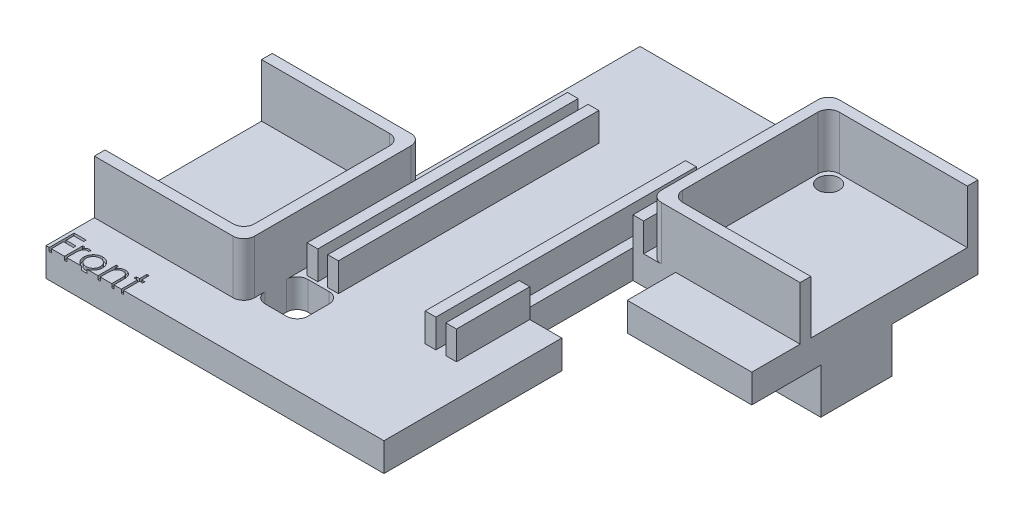
SolidWorks part; units mm, degrees
ref_plane "Front Plane" through (0, 0, 0) normal (0, 0, 1) x (1, 0, 0)
ref_plane "Top Plane" through (0, 0, 0) normal (0, 1, 0) x (1, 0, 0)
ref_plane "Right Plane" through (0, 0, 0) normal (1, 0, 0) x (0, 0, -1)
sketch "Sketch1" plane through (0, 0, 0) normal (0, 1, 0) x (1, 0, 0)
  line L1 (-15, 33) -> (32.5, 33)
  line L2 (-32.5, -1.2) -> (-32.5, -33)
  line L3 (-32.5, -33) -> (15, -33)
  line L4 (32.5, 33) -> (32.5, 1.2)
  line L5 (-15, 15.2308) -> (15, -15.2308) construction
  line L6 (-32.5, -33) -> (32.5, 33) construction
  line L9 (32.5, 1.2) -> (15, 1.2)
  line L10 (15, -33) -> (15, 1.2)
  line L13 (-32.5, -1.2) -> (-15, -1.2)
  line L14 (-15, 33) -> (-15, -1.2)
  point P0 (0, 0)
  dimension "D3" = 17.5
  dimension "D4" = 17.5
  dimension "D5" = 34.2
  dimension "D6" = 34.2
extrude "Boss-Extrude1" add sketch "Sketch1" along normal blind 4
sketch "Sketch2" plane through (0, 4, 0) normal (0, 1, 0) x (1, 0, 0)
  line L0 (32.5, 31.5) -> (14.5, 31.5)
  line L1 (32.5, 33) -> (13, 33)
  line L2 (32.5, 33) -> (32.5, 31.5)
  line L3 (32.5, 8) -> (13, 8)
  line L4 (11.5, 31.5) -> (11.5, 9.5)
  line L5 (13, 30) -> (13, 11)
  line L6 (14.5, 9.5) -> (32.5, 9.5)
  line L7 (32.5, 9.5) -> (32.5, 8)
  line L8 (0, 0) -> (-10.8209, 0) construction
  line L9 (-10.8209, 0) -> (0, 0) construction
  line L10 (0, 0) -> (0, -9.9611) construction
  arc A0 (13, 8) -> (11.5, 9.5) centre (13, 9.5) cw
  arc A1 (13, 11) -> (14.5, 9.5) centre (14.5, 11) ccw
  arc A2 (13, 33) -> (11.5, 31.5) centre (13, 31.5) ccw
  arc A3 (14.5, 31.5) -> (13, 30) centre (14.5, 30) ccw
  dimension "D6" = 1.5
  dimension "D1" = 21
  dimension "D2" = 25
  dimension "D3" = 1.5
  dimension "D4" = 1.5
  dimension "D5" = 1.5
extrude "Boss-Extrude2" add sketch "Sketch2" along normal blind 7.5
sketch "Sketch3" plane through (0, 4, 0) normal (0, 1, 0) x (1, 0, 0)
  line L0 (11.5, 29.5) -> (15, 29.5) construction
  line L1 (11.5, 31.5) -> (11.5, 9.5) construction
  line L2 (15, 29.5) -> (15, 33) construction
  line L3 (32.5, 33) -> (13, 33) construction
  dimension "D1" = 3.5
  dimension "D2" = 3.5
sketch "Sketch5" plane through (0, 4, 0) normal (0, 1, 0) x (1, 0, 0)
  line L0 (-32.5, -2.7) -> (-14.5, -2.7)
  line L1 (-32.5, -1.2) -> (-13, -1.2)
  line L2 (-32.5, -1.2) -> (-32.5, -2.7)
  line L3 (-32.5, -26.2) -> (-13, -26.2)
  line L4 (-11.5, -2.7) -> (-11.5, -24.7)
  line L5 (-13, -4.2) -> (-13, -23.2)
  line L6 (-14.5, -24.7) -> (-32.5, -24.7)
  line L7 (-32.5, -24.7) -> (-32.5, -26.2)
  arc A0 (-13, -1.2) -> (-11.5, -2.7) centre (-13, -2.7) cw
  arc A1 (-13, -26.2) -> (-11.5, -24.7) centre (-13, -24.7) ccw
  arc A2 (-13, -23.2) -> (-14.5, -24.7) centre (-14.5, -23.2) cw
  arc A3 (-14.5, -2.7) -> (-13, -4.2) centre (-14.5, -4.2) cw
  dimension "D6" = 1.5
  dimension "D1" = 21
  dimension "D2" = 25
  dimension "D3" = 1.5
  dimension "D4" = 1.5
  dimension "D5" = 1.5
extrude "Boss-Extrude3" add sketch "Sketch5" along normal blind 7.5
sketch "Sketch6" plane through (0, 4, 0) normal (0, 1, 0) x (1, 0, 0)
  line L0 (-15, -26.2) -> (-15, -22.7) construction
  line L1 (-32.5, -26.2) -> (-13, -26.2) construction
  line L2 (-15, -22.7) -> (-11.5, -22.7) construction
  line L3 (-11.5, -24.7) -> (-11.5, -2.7) construction
  circle A0 centre (-15, -22.7) radius 1.5
  circle A1 centre (15, 29.5) radius 1.5
  dimension "D3" = 3
  dimension "D4" = 3
  dimension "D1" = 3.5
  dimension "D2" = 3.5
extrude "Cut-Extrude1" cut sketch "Sketch6" against normal through all
sketch "Sketch7" plane through (0, 4, 0) normal (0, 1, 0) x (1, 0, 0)
  line L0 (0, 0) -> (0, 34.4926) construction
  line L1 (0, 0) -> (-9, 0) construction
  line L2 (-9, -18.3) -> (-9, 18.3)
  line L3 (-9, 18.3) -> (-10.5, 18.3)
  line L4 (-10.5, 18.3) -> (-10.5, -18.3)
  line L6 (-9, -18.3) -> (-10.5, -18.3)
  line L7 (-9, 2.8922) -> (-8.3, 2.8922) construction
  line L8 (-8.3, 2.8922) -> (-8.3, 1.7687) construction
  line L9 (-7.6, 18.3) -> (-6.1, 18.3)
  line L10 (-7.6, -18.3) -> (-7.6, 18.3)
  line L11 (-7.6, -18.3) -> (-6.1, -18.3)
  line L12 (-6.1, 18.3) -> (-6.1, -18.3)
  line L13 (7.6, -18.3) -> (7.6, 18.3)
  line L14 (7.6, -18.3) -> (6.1, -18.3)
  line L15 (6.1, 18.3) -> (6.1, -18.3)
  line L16 (7.6, 18.3) -> (6.1, 18.3)
  line L17 (9, 18.3) -> (10.5, 18.3)
  line L18 (9, -18.3) -> (9, 18.3)
  line L19 (9, -18.3) -> (10.5, -18.3)
  line L20 (10.5, 18.3) -> (10.5, -18.3)
  dimension "D1" = 9
  dimension "D2" = 18.3
  dimension "D3" = 1.5
  dimension "D4" = 0.7
extrude "Boss-Extrude4" add sketch "Sketch7" along normal blind 4
sketch "Sketch8" plane through (0, 8, 0) normal (0, 1, 0) x (1, 0, 0)
  line L0 (0, 0) -> (9, 0) construction
  line L1 (9, 18.3) -> (9, -18.3) construction
  line L3 (9, -8) -> (9, 8)
  line L4 (9, 8) -> (15, 8)
  line L5 (15, -8) -> (15, 8)
  line L6 (13, 8) -> (32.5, 8) construction
  line L7 (9, -8) -> (15, -8)
  line L8 (15, 0) -> (26.2252, 0) construction
  dimension "D1" = 6
extrude "Cut-Extrude2" cut sketch "Sketch8" against normal through all
sketch "Sketch10" plane through (32.5, 0, 0) normal (1, 0, 0) x (0, 0, -1)
  line L0 (20.5, 0) -> (20.5, -4.95) construction
  line L1 (1.2, 0) -> (33, 0) construction
  line L2 (20.5, -4.95) -> (20.5, -6.35) construction
  dimension "D1" = 4.95
  dimension "D2" = 1.4
sketch "Sketch12" plane through (0, 0, 0) normal (0, -1, 0) x (1, 0, 0)
  line L0 (32.5, -33) -> (32.5, -15.9) construction
  line L1 (32.5, -1.2) -> (32.5, -33) construction
  line L2 (32.5, -10.9) -> (22.5, -10.9)
  line L4 (32.5, -10.9) -> (32.5, -20.9)
  line L5 (32.5, -20.9) -> (22.5, -20.9)
  line L6 (22.5, -10.9) -> (22.5, -20.9)
  line L7 (-32.5, 1.2) -> (-32.5, 18.3) construction
  line L8 (-32.5, 1.2) -> (-32.5, 33) construction
  line L10 (-32.5, 23.3) -> (-22.5, 23.3)
  line L12 (-32.5, 23.3) -> (-32.5, 13.3)
  line L13 (-32.5, 13.3) -> (-22.5, 13.3)
  line L14 (-22.5, 23.3) -> (-22.5, 13.3)
  dimension "D1" = 17.1
  dimension "D2" = 17.1
  dimension "D3" = 10
  dimension "D4" = 10
  dimension "D5" = 10
extrude "Boss-Extrude5" add sketch "Sketch12" along normal blind 6.35
sketch "Sketch14" plane through (0, 4, 0) normal (0, 1, 0) x (1, 0, 0)
  line L0 (-11.5, -24.7) -> (-11.5, -2.7) construction
  line L1 (-10, -18.7) -> (-7, -18.7)
  line L2 (-11.5, -20.2) -> (-11.5, -23.2)
  line L3 (-10, -24.7) -> (-7, -24.7)
  line L4 (-5.5, -20.2) -> (-5.5, -23.2)
  line L5 (-7.6, -18.3) -> (-6.1, -18.3) construction
  line L6 (11.5, 31.5) -> (11.5, 9.5) construction
  line L7 (10, 18.7) -> (7, 18.7)
  line L8 (11.5, 20.2) -> (11.5, 23.2)
  line L9 (10, 24.7) -> (7, 24.7)
  line L10 (5.5, 20.2) -> (5.5, 23.2)
  line L11 (7.6, 18.3) -> (6.1, 18.3) construction
  arc A0 (-7, -24.7) -> (-5.5, -23.2) centre (-7, -23.2) ccw
  arc A1 (-11.5, -23.2) -> (-10, -24.7) centre (-10, -23.2) ccw
  arc A2 (-10, -18.7) -> (-11.5, -20.2) centre (-10, -20.2) ccw
  arc A3 (-7, -18.7) -> (-5.5, -20.2) centre (-7, -20.2) cw
  arc A4 (7, 18.7) -> (5.5, 20.2) centre (7, 20.2) cw
  arc A5 (10, 18.7) -> (11.5, 20.2) centre (10, 20.2) ccw
  arc A6 (11.5, 23.2) -> (10, 24.7) centre (10, 23.2) ccw
  arc A7 (7, 24.7) -> (5.5, 23.2) centre (7, 23.2) ccw
  point P12 (-11.5, -18.7)
  point P27 (5.5, 18.7)
  point P30 (11.5, 18.7)
  point P33 (11.5, 24.7)
  point P36 (5.5, 24.7)
  dimension "D3" = 1.5
  dimension "D8" = 1.5
  dimension "D1" = 6
  dimension "D2" = 6
  dimension "D4" = 0.4
  dimension "D5" = 0.4
  dimension "D6" = 6
  dimension "D7" = 6
extrude "Cut-Extrude3" cut sketch "Sketch14" against normal through all
sketch "Sketch16" plane through (0, 4, 0) normal (0, 1, 0) x (1, 0, 0)
  line L0 (-32.5, -33) -> (-11.1838, -33) construction
  line L1 (-32.5, -33) -> (15, -33) construction
  text T0 "Front"
extrude "Cut-Extrude4" cut sketch "Sketch16" against normal blind 0.5
